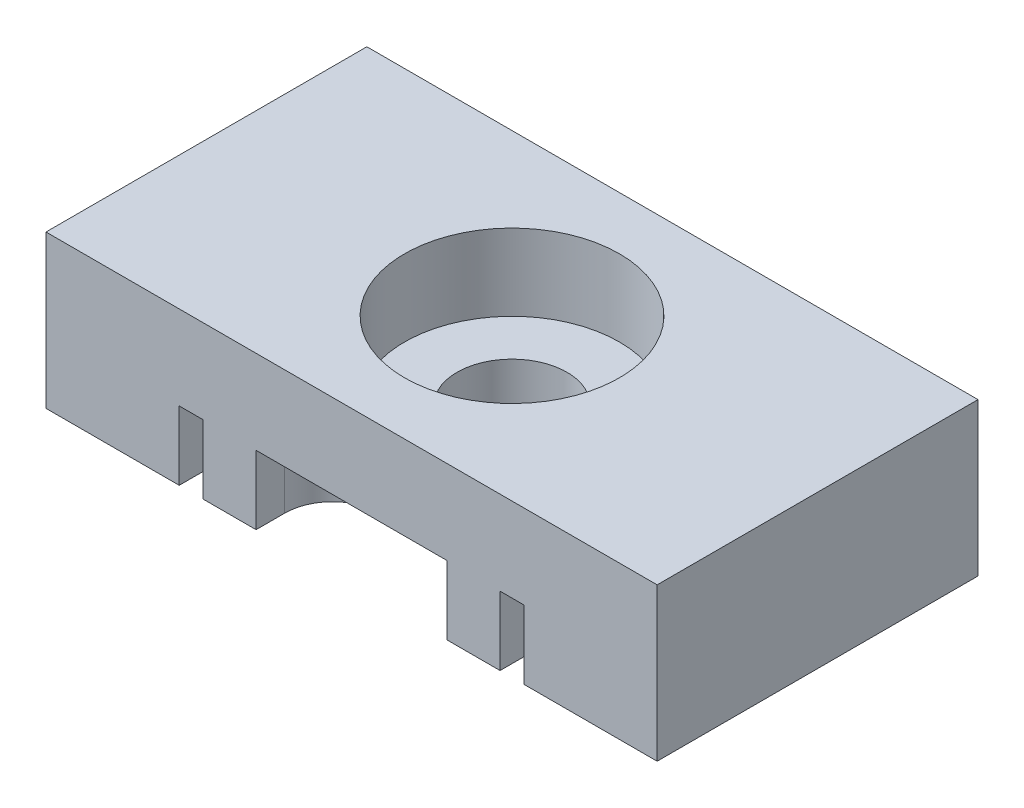
SolidWorks part; units mm, degrees
material "Nylon 6/10"
ref_plane "Front Plane" through (0, 0, 0) normal (0, 0, 1) x (1, 0, 0)
ref_plane "Top Plane" through (0, 0, 0) normal (0, 1, 0) x (1, 0, 0)
ref_plane "Right Plane" through (0, 0, 0) normal (1, 0, 0) x (0, 0, -1)
sketch "Sketch1" plane through (0, 0, 0) normal (0, 1, 0) x (1, 0, 0)
  line L1 (-10.16, -5.334) -> (10.16, -5.334)
  line L2 (-10.16, -5.334) -> (-10.16, 5.334)
  line L3 (-10.16, 5.334) -> (10.16, 5.334)
  line L4 (10.16, -5.334) -> (10.16, 5.334)
  line L5 (-10.16, -5.334) -> (10.16, 5.334) construction
  line L6 (-10.16, 5.334) -> (10.16, -5.334) construction
  point P0 (0, 0)
  dimension "D1" = 20.32
  dimension "D2" = 10.668
extrude "Base" add sketch "Sketch1" along normal blind 5.08
sketch "Sketch2" plane through (0, 0, 0) normal (0, -1, 0) x (1, 0, 0)
  line L0 (-5.334, 5.334) -> (-5.334, 3.8608) construction
  line L1 (-10.16, 5.334) -> (10.16, 5.334) construction
  line L2 (-4.9371, 5.334) -> (-4.9371, 3.8608)
  line L3 (-5.7309, 5.334) -> (-5.7309, 3.8608)
  line L4 (5.334, 5.334) -> (5.334, 3.8608) construction
  line L5 (5.7309, 5.334) -> (5.7309, 3.8608)
  line L6 (4.9371, 5.334) -> (4.9371, 3.8608)
  line L7 (0, 0) -> (0, 225.9023) construction
  arc A0 (-4.9371, 5.334) -> (-5.7309, 5.334) centre (-5.334, 5.334) ccw
  arc A1 (-5.7309, 3.8608) -> (-4.9371, 3.8608) centre (-5.334, 3.8608) ccw
  arc A2 (5.7309, 5.334) -> (4.9371, 5.334) centre (5.334, 5.334) ccw
  arc A3 (4.9371, 3.8608) -> (5.7309, 3.8608) centre (5.334, 3.8608) ccw
  point P4 (-5.334, 4.5974)
  point P9 (5.334, 4.5974)
  dimension "D1" = 0.7937
  dimension "D2" = 10.668
  dimension "D3" = 1.4732
extrude "BoxSlots" cut sketch "Sketch2" against normal blind 2.286
hole_wizard "MoutingHole" positions "Sketch6" profile "Sketch5" counterbore size "#6" standard "ANSI Inch" end condition through all
sketch "Sketch6" plane through (0, 5.08, 0) normal (0, 1, 0) x (1, 0, 0)
  point P0 (0, 0)
sketch "Sketch5" plane through (0, 5.08, 0) normal (1, 0, 0) x (0, 0, 1)
  line L0 (0, 0) -> (0, 5.08)
  line L1 (0, 5.08) -> (1.8288, 5.08)
  line L3 (1.8288, 5.08) -> (1.8288, 2.54)
  line L4 (1.8288, 2.54) -> (3.5725, 2.54)
  line L5 (3.5725, 2.54) -> (3.5725, 0)
  line L7 (3.5725, 0) -> (0, 0)
  line L11 (0, -6.35) -> (0, 107.95) construction
  dimension "Thru Hole Dia." = 3.6576
  dimension "Thru Hole Depth" = 5.08
  dimension "C'Bore Dia." = 7.145
  dimension "C'Bore Depth" = 2.54
sketch "Sketch7" plane through (0, 0, 0) normal (0, -1, 0) x (1, 0, 0)
  line L0 (-4.9371, 5.334) -> (4.9371, 5.334) construction
  line L1 (-3.175, 5.334) -> (3.175, 5.334)
  line L2 (-3.175, 5.334) -> (-3.175, 4.3815)
  line L3 (-1.5875, 2.794) -> (1.5875, 2.794)
  line L4 (3.175, 5.334) -> (3.175, 4.3815)
  line L5 (-3.175, 5.334) -> (3.175, 2.794) construction
  line L6 (-3.175, 2.794) -> (3.175, 5.334) construction
  arc A0 (-1.5875, 2.794) -> (-3.175, 4.3815) centre (-1.5875, 4.3815) cw
  arc A1 (1.5875, 2.794) -> (3.175, 4.3815) centre (1.5875, 4.3815) ccw
  point P0 (0, 4.064)
  dimension "D3" = 1.5875
  dimension "D1" = 6.35
  dimension "D2" = 2.54
extrude "Cut-Extrude1" cut sketch "Sketch7" against normal blind 2.286
